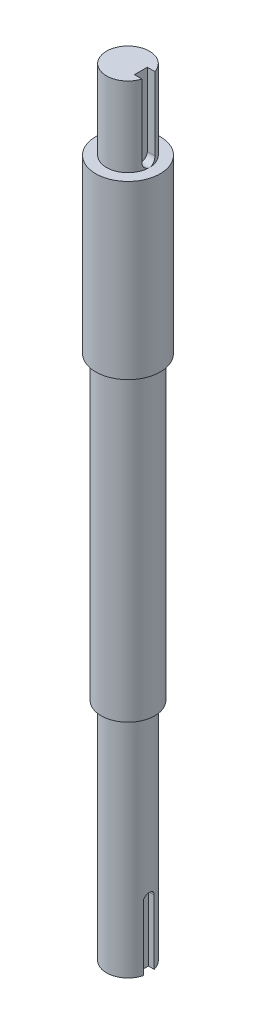
SolidWorks part; units mm, degrees
ref_plane "Front Plane" through (0, 0, 0) normal (0, 0, 1) x (1, 0, 0)
ref_plane "Top Plane" through (0, 0, 0) normal (0, 1, 0) x (1, 0, 0)
ref_plane "Right Plane" through (0, 0, 0) normal (1, 0, 0) x (0, 0, -1)
sketch "Sketch1" plane through (0, 0, 0) normal (1, 0, 0) x (0, 0, -1)
  line L0 (0, 26) -> (0, -336) construction
  line L1 (0, 26) -> (10, 26)
  line L2 (10, 26) -> (10, -11)
  line L3 (10, -11) -> (15, -11)
  line L4 (15, -11) -> (15, -91)
  line L5 (15, -91) -> (12.5, -91)
  line L6 (12.5, -91) -> (12.5, -231)
  line L7 (12.5, -231) -> (10, -231)
  line L8 (10, -231) -> (10, -242.2)
  line L9 (10, -336) -> (0, -336)
  line L10 (0, 26) -> (0, -336)
  line L14 (10, -242.2) -> (10, -336)
  line L17 (0, 38.6816) -> (0, -307.0732) construction
  dimension "D1" = 20
  dimension "D2" = 30
  dimension "D3" = 80
  dimension "D4" = 11
  dimension "D9" = 37
  dimension "D5" = 25
  dimension "D6" = 20
  dimension "D8" = 140
  dimension "D7" = 105
revolve "Revolve1" add sketch "Sketch1" angle 360 about L0
sketch "Sketch2" plane through (0, 0, 0) normal (1, 0, 0) x (0, 0, -1)
  line L0 (0, 26) -> (0, -8) construction
  line L1 (3, 26) -> (3, -8)
  line L2 (-3, 26) -> (-3, -8)
  line L3 (10, -11) -> (-10, -11) construction
  line L4 (10, 26) -> (-10, 26) construction
  arc A0 (3, 26) -> (-3, 26) centre (0, 26) ccw
  arc A1 (-3, -8) -> (3, -8) centre (0, -8) ccw
  point P3 (0, 9)
  dimension "D1" = 6
extrude "Cut-Extrude1" cut sketch "Sketch2" along normal through all from offset 6
sketch "Sketch3" plane through (0, 0, 0) normal (1, 0, 0) x (0, 0, -1)
  line L0 (0, -306) -> (0, -336) construction
  line L1 (2.5, -306) -> (2.5, -336)
  line L2 (-2.5, -306) -> (-2.5, -336)
  line L5 (-10, -336) -> (10, -336) construction
  arc A0 (2.5, -306) -> (-2.5, -306) centre (0, -306) ccw
  arc A1 (-2.5, -336) -> (2.5, -336) centre (0, -336) ccw
  point P3 (0, -321)
  dimension "D1" = 5
  dimension "D2" = 30
extrude "Cut-Extrude2" cut sketch "Sketch3" against normal blind 3 from offset 10
sketch "Sketch4" plane through (0, -336, 0) normal (0, -1, 0) x (1, 0, 0)
  circle A0 centre (0, 0) radius 4
  dimension "D1" = 8
extrude "Cut-Extrude3" cut sketch "Sketch4" against normal blind 30
equation "\"d_ext_rouleau\"= 90"
equation "\"epaisseur_rouleau\"=80"
equation "\"alesage-rouleau\"= 52"
equation "\"jeu_dent_rouleau\"= 2"
equation "\"profondeur_dent_rouleau\"=4"
equation "\"n_dent_roueau\"= 15"
equation "\"d_ext_roulement_rouleau\"= 42"
equation "\"d_int_roulement_rouleau\"= 20"
equation "\"B_roulement_rouleau\"= 12"
equation "\"r_roulement_rouleau\"= 0.6"
equation "\"d_bille_roulement_rouleau\"= 8"
equation "\"F_anneau_alesage_rouleau\"=1.85"
equation "\"G_anneau_alesage_rouleau\"=47.5"
equation "\"K_anneau_alesage_rouleau\"=3.75"
equation "\"d_vis_flasque_rouleau\"=5"
equation "\"l-x_vis_flasque_rouleau\"=4"
equation "\"g_anneau_arbre_rouleau\"=19"
equation "\"f_anneau_arbre_rouleau\"=1.3"
equation "\"k_anneau_arbre_rouleau\"=1.5"
equation "\"h_matrice\"= 22"
equation "\"d_matrice\"= 220"
equation "\"d_granulat\"= 8"
equation "\"zone_vide_matrice\" = 48"
equation "\"d_alesage_matrice\"=20"
equation "\"a_clavette_alesage_matrice\"=6"
equation "\"entrax_vis_rouleau\"=65"
equation "\"D1@Sketch1\" = \"d_int_roulement_bc_matrice\""
equation "\"D2@Sketch1\"= \"d_int_roulement_bc_matrice\" + 10"
equation "\"h_epaulement_arbre_matrice\" = 80"
equation "\"D3@Sketch1\"=\"h_epaulement_arbre_matrice\""
equation "\"D4@Sketch1\"=\"h_matrice\"/2"
equation "\"h_polie_matrice\" = 40"
equation "\"l_arbre_matrice\" = 300"
equation "\"D9@Sketch1\"=\"h_matrice\"+15"
equation "\"D1@Sketch2\"=\"a_clavette_alesage_matrice\""
equation "\"D19@Cut-Extrude1\"=\"j_clavette_arbre_matrice\""
equation "\"j_clavette_arbre_matrice\" = 6"
equation "\"f_anneaux_arbre_matrice\" = 1.3"
equation "\"g_anneaux_arbre_matrice\" = 19"
equation "\"B_roulement_bc_arbre_matrice\"= 10"
equation "\"e_anneaux_arbre_matrice\" = 1.2"
equation "\"d_int_polie_matrice\" = 16"
equation "\"d_int_ecrou_encouch_matrice\" = 20"
equation "\"d_ext_ecrou_encouch_matrice\" = 32"
equation "\"b_ecrou_encouch_matrice\" = 6"
equation "\"s_ecrou_encouch_matrice\" = 4"
equation "\"G_ecrou_encouch_matrice\" = 1"
equation "\"E_ecrou_encouch_matrice\" = 4"
equation "\"d_int_roulement_conique_matrice\"=25"
equation "\"d_ext_roulement_conique_matrice\"=52"
equation "\"b_roulement_conique_matrice\"=16.25"
equation "\"d_int_roulement_bc_matrice\"=20"
equation "\"d_ext_roulement_bc_matrice\"=42"
equation "\"b_roulement_bc_matrice\" = 12"
equation "\"d_tube_sup_carter\"=244.5"
equation "\"e_tube_sup_carter\"=12"
equation "\"d_tube_inf_catrer\"= 168.3"
equation "\"e_tube_inf_carter\"= 6"
equation "\"d_tube_inf_carter_cache\" = 244.5"
equation "\"e_tube_inf_carter_cache\" = 8"
equation "\"d_tube_sup_carter_cache\" = 133"
equation "\"e_tube_sup_carter_cache\" = 4"
equation "\"h_tube_trimee\" = 40"
equation "\"e_tole\" = 8"
equation "\"entraxe_vis_carter\" = 196"
equation "\"D5@Sketch1\"=\"d_int_roulement_conique_matrice\""
equation "\"D6@Sketch1\"=\"d_int_roulement_bc_matrice\""
